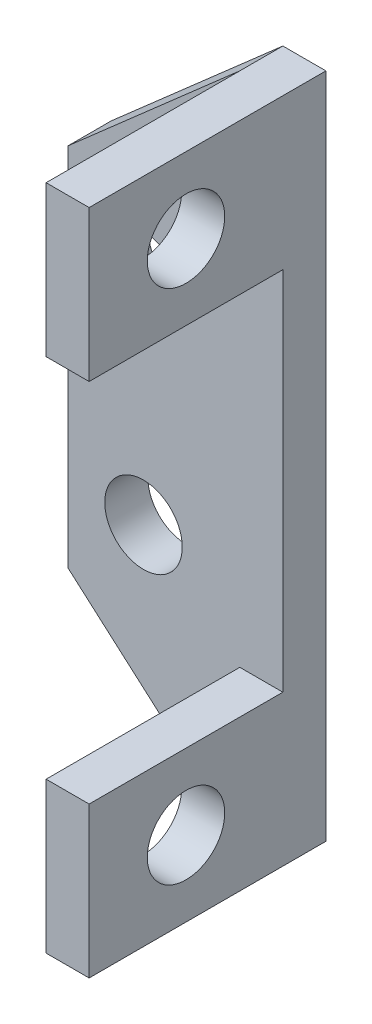
SolidWorks part; units mm, degrees
ref_plane "Front Plane" through (0, 0, 0) normal (0, 0, 1) x (1, 0, 0)
ref_plane "Top Plane" through (0, 0, 0) normal (0, 1, 0) x (1, 0, 0)
ref_plane "Right Plane" through (0, 0, 0) normal (1, 0, 0) x (0, 0, -1)
sketch "Sketch2" plane through (0, 0, 0) normal (0, 0, 1) x (1, 0, 0)
  line L1 (-9.9744, 7) -> (0, 7)
  line L2 (-9.9744, 7) -> (-9.9744, 24)
  line L3 (-9.9744, 24) -> (0, 24)
  line L4 (0, 7) -> (0, 24)
  line L6 (-6.4744, 10.5) -> (-9.9744, 10.5) construction
  line L7 (-6.4744, 10.5) -> (-6.4744, 7) construction
  line L8 (-9.9744, 15.5) -> (0, 15.5) construction
  line L9 (-6.4744, 10.5) -> (-6.4744, 20.5) construction
  line L10 (0, 7) -> (0, 0)
  line L11 (0, 0) -> (-2, 0)
  line L12 (-2, 0) -> (-9.9744, 7)
  line L13 (0, 24) -> (0, 31)
  line L14 (0, 31) -> (-2, 31)
  line L15 (-2, 31) -> (-9.9744, 24)
  circle A1 centre (-6.4744, 10.5) radius 1.4 construction
  point P15 (-6.4744, 15.5)
  dimension "D6" = 2.8
  dimension "D2" = 7
  dimension "D3" = 2
  dimension "D1" = 9.9744
  dimension "D4" = 17
  dimension "D5" = 5
extrude "Boss-Extrude1" add sketch "Sketch2" along normal blind 2 contours L12 L11 L10 L1 | L14 L15 L3 L13 | L1 L4 L3 L2 region at (-4.9872, 15.5, 0) region at (-3.4362, 4.2769, 0) region at (-3.4362, 26.7231, 0)
sketch "Sketch9" plane through (0, 0, 2) normal (0, 0, 1) x (1, 0, 0)
  line L0 (-9.9744, 15.5) -> (0, 15.5) construction
  line L1 (-9.9744, 7) -> (-9.9744, 24) construction
  point P7 (-6.4744, 10.5)
  point P18 (-6.4744, 20.5)
hole_wizard "M3 Clearance Hole1" positions "Sketch9" profile "Sketch4" hole size "M3" standard "ANSI Metric" end condition through all
sketch "Sketch4" plane through (-6.4744, 10.5, 2) normal (1, 0, 0) x (0, -1, 0)
  line L0 (0, 0) -> (0, 2)
  line L1 (0, 2) -> (1.8, 2)
  line L2 (1.8, 2) -> (1.8, 0)
  line L5 (1.8, 0) -> (0, 0)
  line L11 (0, -6.35) -> (0, 107.95) construction
  dimension "Thru Hole Dia." = 3.6
  dimension "Thru Hole Depth" = 2
sketch "Sketch6" plane through (0, 0, 2) normal (0, 0, 1) x (1, 0, 0)
  line L0 (-9.9744, 15.5) -> (0, 15.5) construction
  line L1 (0, 24) -> (-2, 24)
  line L2 (0, 24) -> (0, 31)
  line L3 (0, 31) -> (-2, 31)
  line L4 (-2, 24) -> (-2, 31)
  line L7 (0, 0) -> (-2, 0)
  line L8 (-2, 7) -> (-2, 0)
  line L9 (0, 7) -> (-2, 7)
  line L10 (0, 7) -> (0, 0)
  line L12 (0, 31) -> (0, 0) construction
  line L13 (-9.9744, 7) -> (-9.9744, 24) construction
  line L14 (0, 31) -> (-2, 31) construction
  dimension "D1" = 7
  dimension "D2" = 2
extrude "Boss-Extrude2" add sketch "Sketch6" along normal blind 9
sketch "Sketch10" plane through (-2, 0, 0) normal (-1, 0, 0) x (0, 0, 1)
  line L0 (11, 27.5) -> (2, 27.5) construction
  line L1 (11, 31) -> (11, 24) construction
  line L2 (2, 31) -> (2, 24) construction
  line L4 (11, 3.5) -> (2, 3.5) construction
  line L5 (11, 7) -> (11, 0) construction
  line L6 (2, 7) -> (2, 0) construction
  point P0 (6.5, 3.5)
  point P2 (6.5, 27.5)
  point P3 (6.5, 3.5)
  point P24 (6.5, 3.5)
hole_wizard "M3 Clearance Hole2" positions "Sketch10" profile "Sketch8" hole size "M3" standard "ANSI Metric" end condition through all
sketch "Sketch8" plane through (-2, 3.5, 6.5) normal (0, 1, 0) x (0, 0, 1)
  line L0 (0, 0) -> (0, 2)
  line L1 (0, 2) -> (1.8, 2)
  line L2 (1.8, 2) -> (1.8, 0)
  line L5 (1.8, 0) -> (0, 0)
  line L11 (0, -6.35) -> (0, 107.95) construction
  dimension "Thru Hole Dia." = 3.6
  dimension "Thru Hole Depth" = 2
equation "\"width\" = 7.30441 + 2.67"
equation "\"D1@Sketch2\"=\"width\""
